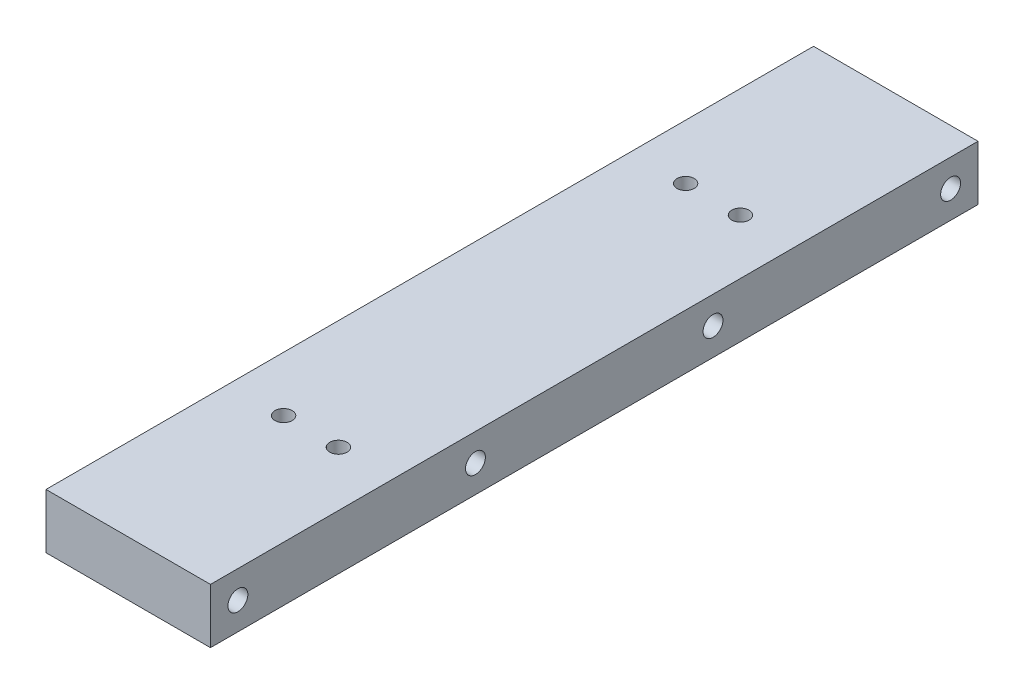
SolidWorks part; units mm, degrees
ref_plane "Front Plane" through (0, 0, 0) normal (0, 0, 1) x (1, 0, 0)
ref_plane "Top Plane" through (0, 0, 0) normal (0, 1, 0) x (1, 0, 0)
ref_plane "Right Plane" through (0, 0, 0) normal (1, 0, 0) x (0, 0, -1)
sketch "Sketch2" plane through (0, 0, 0) normal (0, 1, 0) x (1, 0, 0)
  line L0 (0, 0) -> (28.575, 0)
  line L1 (28.575, 0) -> (28.575, 133.35)
  line L2 (28.575, 133.35) -> (0, 133.35)
  line L3 (0, 133.35) -> (0, 0)
  dimension "D1" = 133.35
  dimension "D2" = 28.575
extrude "Boss-Extrude1" add sketch "Sketch2" along normal blind 9.525
sketch "Sketch3" plane through (28.575, 0, 0) normal (1, 0, 0) x (0, 0, -1)
  line L0 (0, 9.525) -> (0, 0) construction
  line L1 (0, 9.525) -> (133.35, 9.525) construction
  point P0 (4.7625, 4.7625)
  dimension "D1" = 4.7625
  dimension "D2" = 4.7625
sketch "Sketch4" plane through (28.575, 0, 0) normal (1, 0, 0) x (0, 0, -1)
  point P0 (4.7625, 4.7625)
hole_wizard "#5 Clearance Hole1" positions "Sketch4" profile "Sketch5" hole size "#5" standard "ANSI Inch"
sketch "Sketch5" plane through (28.575, 4.7625, -4.7625) normal (0, 1, 0) x (0, 0, -1)
  line L0 (0, 0) -> (0, 13.7378)
  line L1 (0, 13.7378) -> (1.7272, 12.7)
  line L2 (1.7272, 12.7) -> (1.7272, 0)
  line L5 (1.7272, 0) -> (0, 0)
  line L10 (0, 13.7378) -> (-1.7272, 12.7) construction
  line L11 (0, -6.35) -> (0, 107.95) construction
  dimension "Hole Dia." = 3.4544
  dimension "Hole Depth" = 12.7
  dimension "Drill Angle" = 118
pattern_linear "LPattern1" count 4 spacing 41.275 along (0, 0, -1) of "#5 Clearance Hole1"
sketch "Sketch6" plane through (0, 0, 0) normal (-1, 0, 0) x (0, 0, 1)
  line L0 (-133.35, 9.525) -> (-133.35, 0) construction
  line L1 (-133.35, 9.525) -> (0, 9.525) construction
  point P0 (-128.5875, 4.7625)
  dimension "D1" = 4.7625
  dimension "D2" = 4.7625
hole_wizard "#5 Clearance Hole2" positions "Sketch6" profile "Sketch7" hole size "#5" standard "ANSI Inch"
sketch "Sketch7" plane through (0, 4.7625, -128.5875) normal (0, 1, 0) x (0, 0, 1)
  line L0 (0, 0) -> (0, 13.7378)
  line L1 (0, 13.7378) -> (1.7272, 12.7)
  line L2 (1.7272, 12.7) -> (1.7272, 0)
  line L5 (1.7272, 0) -> (0, 0)
  line L10 (0, 13.7378) -> (-1.7272, 12.7) construction
  line L11 (0, -6.35) -> (0, 107.95) construction
  dimension "Hole Dia." = 3.4544
  dimension "Hole Depth" = 12.7
  dimension "Drill Angle" = 118
pattern_linear "LPattern2" count 4 spacing 41.275 along (0, 0, 1) of "#5 Clearance Hole2"
sketch "Sketch8" plane through (0, 0, 0) normal (0, -1, 0) x (1, 0, 0)
  line L0 (0, 0) -> (14.2875, 0)
  line L1 (0, 0) -> (28.575, 0) construction
  line L2 (28.575, -133.35) -> (0, -133.35) construction
  line L3 (0, -133.35) -> (0, 0) construction
  line L4 (28.575, 0) -> (28.575, -133.35) construction
  circle A0 centre (9.525, -31.75) radius 1.5
  circle A1 centre (9.525, -101.6) radius 1.5
  circle A2 centre (19.05, -101.6) radius 1.5
  circle A3 centre (19.05, -31.75) radius 1.5
  point P5 (9.525, -31.75)
  point P6 (9.525, -101.6)
  point P15 (19.05, -31.75)
  point P16 (19.05, -101.6)
  dimension "D5" = 3
  dimension "D6" = 3
  dimension "D11" = 3
  dimension "D12" = 3
  dimension "D1" = 31.75
  dimension "D2" = 31.75
  dimension "D3" = 9.525
  dimension "D4" = 9.525
  dimension "D7" = 9.525
  dimension "D8" = 9.525
  dimension "D9" = 31.75
  dimension "D10" = 31.75
extrude "Cut-Extrude2" cut sketch "Sketch8" against normal through all contours A0 | A1 | A2 | A3 region at (9.525, 0, -31.75) region at (9.525, 0, -101.6)
